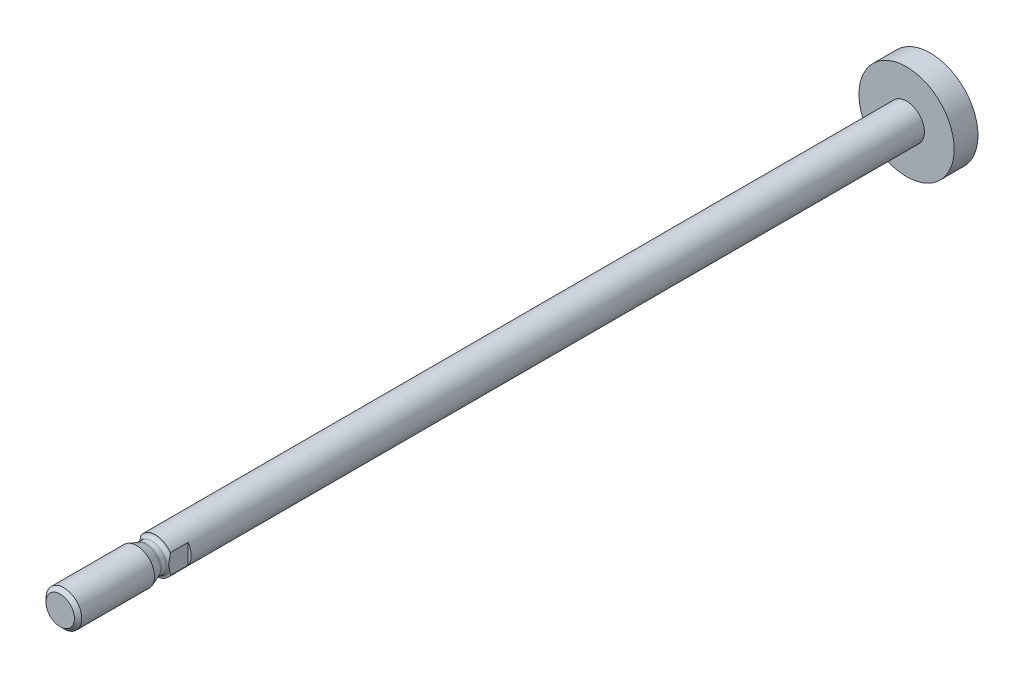
SolidWorks part; units mm, degrees
ref_plane "Front Plane" through (0, 0, 0) normal (0, 0, 1) x (1, 0, 0)
ref_plane "Top Plane" through (0, 0, 0) normal (0, 1, 0) x (1, 0, 0)
ref_plane "Right Plane" through (0, 0, 0) normal (1, 0, 0) x (0, 0, -1)
sketch "Sketch1" plane through (0, 0, 0) normal (1, 0, 0) x (0, 0, -1)
  line L0 (-5, 0) -> (-5, 3)
  line L1 (-5, 3) -> (121.2, 3)
  line L2 (121.2, 3) -> (121.2, 8)
  line L3 (121.2, 8) -> (125.2, 8)
  line L4 (125.2, 8) -> (125.2, 0)
  line L5 (125.2, 0) -> (-5, 0)
  line L6 (125.2, 0) -> (-5, 0) construction
revolve "Revolve1" add sketch "Sketch1" angle 360 about L6 reverse direction yes
sketch "Sketch2" plane through (0, 0, 0) normal (1, 0, 0) x (0, 0, -1)
  line L0 (-21, 0) -> (-21, 2.3865)
  line L1 (-21, 2.3865) -> (-20.3865, 3)
  line L2 (-20.3865, 3) -> (-8.1485, 3)
  line L3 (-8.1485, 3) -> (-6.5994, 2.4362)
  line L4 (-6.3942, 2.4) -> (-5.6, 2.4)
  line L5 (-5, 3) -> (-4, 3)
  line L6 (-4, 3) -> (-4, 0)
  line L7 (-4, 0) -> (-21, 0)
  line L8 (-4, 0) -> (-21, 0) construction
  arc A0 (-6.5994, 2.4362) -> (-6.3942, 2.4) centre (-6.3942, 3) ccw
  arc A1 (-5.6, 2.4) -> (-5, 3) centre (-5.6, 3) ccw
revolve "Revolve2" add sketch "Sketch2" angle 360 about L8 reverse direction yes
cosmetic thread "Cosmetic Thread1" parameters "D1"=12.8515, "D2"=4.773
ref_plane "Plane1" through (0, 0, 5) normal (0, 0, 1) x (1, 0, 0)
ref_plane "Plane2" through (0, 0, 2) normal (0, 0, 1) x (1, 0, 0)
sketch "Sketch3" plane through (0, 0, 2) normal (0, 0, 1) x (1, 0, 0)
  line L0 (-5, 10) -> (-5, -5)
  line L1 (-5, -5) -> (-2.5, -5)
  line L2 (-2.5, -5) -> (-2.5, 5)
  line L3 (-2.5, 5) -> (2.5, 5)
  line L4 (2.5, 5) -> (2.5, -5)
  line L5 (2.5, -5) -> (5, -5)
  line L6 (5, -5) -> (5, 10)
  line L7 (5, 10) -> (-5, 10)
extrude "Cut-Extrude1" cut sketch "Sketch3" along normal blind 4
ref_plane "Plane3" through (0, 0, -255) normal (0, 0, 1) x (1, 0, 0)
ref_plane "Plane4" through (0, 0, 16) normal (0, 0, 1) x (1, 0, 0)
ref_plane "Plane5" through (0, 0, 11.2) normal (0, 0, 1) x (1, 0, 0)
ref_plane "FDT_KSAUFSATZ XY" through (0, 0, 11.2) normal (0, 0, 1) x (1, 0, 0)
ref_plane "FDT_KSAUFSATZ XZ" through (0, 0, 0) normal (0, 1, 0) x (1, 0, 0)
ref_plane "FDT_KSAUFSATZ YZ" through (0, 0, 0) normal (-1, 0, 0) x (0, 0, 1)
ref_axis "FDT_KSAUFSATZ X" through (80.9, 0, 11.2) along (-1, 0, 0)
ref_axis "FDT_KSAUFSATZ Y" through (0, 50, 11.2) along (0, -1, 0)
ref_axis "FDT_KSAUFSATZ Z" through (0, 0, 80.9) along (0, 0, -1)
sketch3d "FDT_KSAUFSATZ"
  point P0 (0, 0, 11.2)
ref_plane "FDT_NUT XY" through (0, 0, 11.2) normal (0, 0, 1) x (1, 0, 0)
ref_plane "FDT_NUT XZ" through (0, 0, 0) normal (0, 1, 0) x (1, 0, 0)
ref_plane "FDT_NUT YZ" through (0, 0, 0) normal (-1, 0, 0) x (0, 0, 1)
ref_axis "FDT_NUT X" through (80.9, 0, 11.2) along (-1, 0, 0)
ref_axis "FDT_NUT Y" through (0, 50, 11.2) along (0, -1, 0)
ref_axis "FDT_NUT Z" through (0, 0, 80.9) along (0, 0, -1)
sketch3d "FDT_NUT"
  point P0 (0, 0, 11.2)
ref_plane "KS XY" through (0, 0, 0) normal (0, 0, -1) x (-1, 0, 0)
ref_plane "KS XZ" through (0, 0, 0) normal (0, 1, 0) x (1, 0, 0)
ref_plane "KS YZ" through (0, 0, 0) normal (1, 0, 0) x (0, 0, -1)
ref_axis "KS X" through (-80.9, 0, 0) along (1, 0, 0)
ref_axis "KS Y" through (0, 50, 0) along (0, -1, 0)
ref_axis "KS Z" through (0, 0, -80.9) along (0, 0, 1)
sketch3d "KS"
  point P0 (0, 0, 0)
ref_plane "NUT1 XY" through (0, 0, 16) normal (0, 0, 1) x (1, 0, 0)
ref_plane "NUT1 XZ" through (0, 0, 0) normal (0, -1, 0) x (-1, 0, 0)
ref_plane "NUT1 YZ" through (0, 0, 0) normal (1, 0, 0) x (0, 0, -1)
ref_axis "NUT1 X" through (-80.9, 0, 16) along (1, 0, 0)
ref_axis "NUT1 Y" through (0, -50, 16) along (0, 1, 0)
ref_axis "NUT1 Z" through (0, 0, 80.9) along (0, 0, -1)
sketch3d "NUT1"
  point P0 (0, 0, 16)
